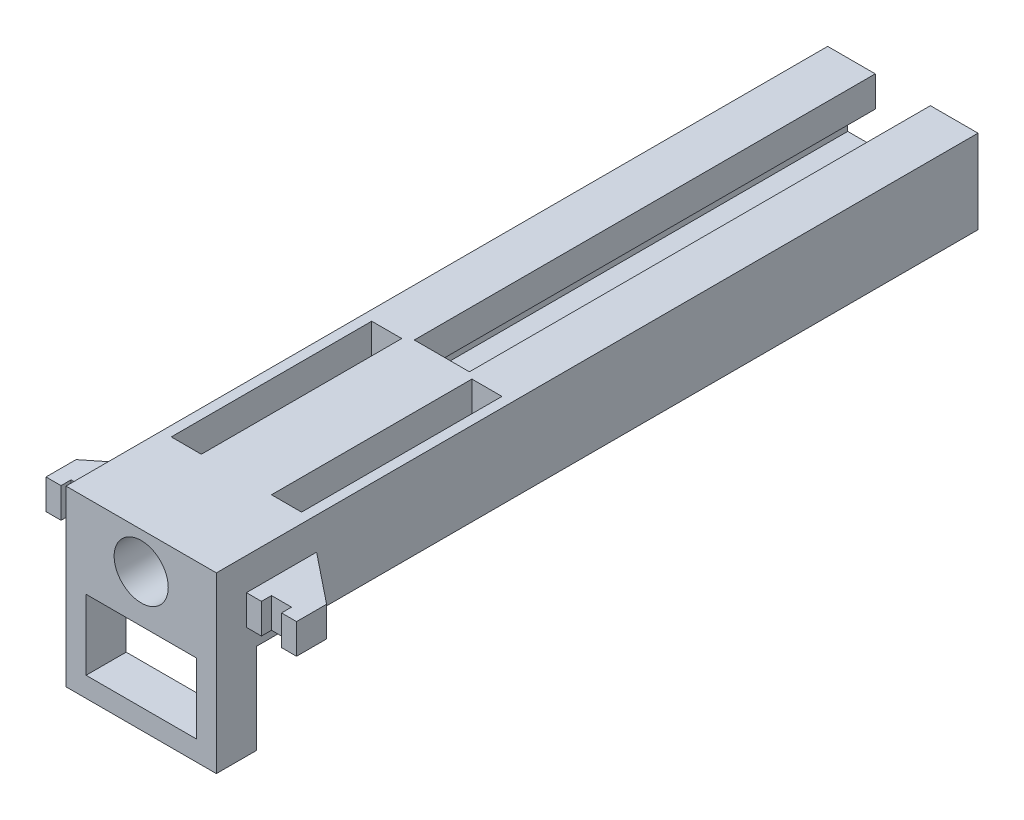
SolidWorks part; units mm, degrees
ref_plane "Front Plane" through (0, 0, 0) normal (0, 0, 1) x (1, 0, 0)
ref_plane "Top Plane" through (0, 0, 0) normal (0, 1, 0) x (1, 0, 0)
ref_plane "Right Plane" through (0, 0, 0) normal (1, 0, 0) x (0, 0, -1)
sketch "Sketch9" plane through (0, 0, 0) normal (0, 0, 1) x (1, 0, 0)
  line L1 (-7.5, 8.35) -> (7.5, 8.35)
  line L2 (-7.5, 8.35) -> (-7.5, 0)
  line L3 (-7.5, 0) -> (7.5, 0)
  line L4 (7.5, 8.35) -> (7.5, 0)
  line L5 (-7.5, 8.35) -> (7.5, 0) construction
  line L6 (-7.5, 0) -> (7.5, 8.35) construction
  point P0 (0, 4.175)
  point P19 (0, 0)
  dimension "D1" = 8.35
  dimension "D2" = 15
extrude "Boss-Extrude4" add sketch "Sketch9" along normal blind 76
sketch "Sketch7" plane through (0, 0, 0) normal (0, 0, 1) x (1, 0, 0)
  line L0 (-5.5, 2) -> (-5.5, 5.3)
  line L1 (-5.5, 5.3) -> (-2.75, 5.3)
  line L2 (-2.75, 5.3) -> (-2.75, 8.35)
  line L3 (-2.75, 8.35) -> (2.75, 8.35) construction
  line L4 (2.75, 8.35) -> (2.75, 5.3)
  line L5 (2.75, 5.3) -> (5.5, 5.3)
  line L6 (5.5, 5.3) -> (5.5, 2)
  line L7 (5.5, 2) -> (-5.5, 2)
  line L9 (7.5, 8.35) -> (-7.5, 8.35) construction
  line L11 (7.5, 0) -> (7.5, 8.35) construction
  line L13 (-2.75, 8.35) -> (2.75, 8.35)
  dimension "D1" = 3.3
  dimension "D2" = 2
  dimension "D3" = 11
  dimension "D4" = 5.5
  dimension "D5" = 2
extrude "Cut-Extrude4" cut sketch "Sketch7" along normal blind 46
sketch "Sketch10" plane through (0, 0, 76) normal (0, 0, 1) x (1, 0, 0)
  line L0 (5.5, 2) -> (-5.5, 2) construction
  circle A0 centre (0, 4.7) radius 2.7
  dimension "D1" = 5.4
extrude "Cut-Extrude5" cut sketch "Sketch10" against normal up to surface (30 mm away) up to face at (0, 5.2375, 46)
sketch "Sketch12" plane through (7.5, 0, 0) normal (1, 0, 0) x (0, 0, -1)
  line L0 (-76, 0) -> (0, 0) construction
  line L1 (-73, 5.14) -> (-70, 5.14)
  line L2 (-73, 5.14) -> (-73, 2.14)
  line L3 (-73, 2.14) -> (-70, 2.14)
  line L4 (-70, 5.14) -> (-70, 2.14)
  line L5 (-73, 5.14) -> (-70, 2.14) construction
  line L6 (-73, 2.14) -> (-70, 5.14) construction
  line L7 (-76, 0) -> (-76, 8.35) construction
  point P0 (-71.5, 3.64)
  dimension "D1" = 3
  dimension "D2" = 3
  dimension "D3" = 2.14
  dimension "D4" = 3
extrude "Boss-Extrude5" add sketch "Sketch12" along normal blind 5
ref_plane "Plane1" through (0, 0, 0) normal (1, 0, 0) x (0, 0, -1)
sketch "Sketch13" plane through (0, 0, 73) normal (0, 0, 1) x (1, 0, 0)
  line L1 (9, 5.14) -> (11, 5.14)
  line L2 (9, 5.14) -> (9, 2.14)
  line L3 (9, 2.14) -> (11, 2.14)
  line L4 (11, 5.14) -> (11, 2.14)
  line L6 (12.5, 5.14) -> (7.5, 5.14) construction
  line L7 (12.5, 2.14) -> (7.5, 2.14) construction
  point P8 (10, 5.14)
  point P9 (10, 5.14)
  dimension "D2" = 2
extrude "Cut-Extrude6" cut sketch "Sketch13" against normal blind 1
mirror "Mirror2" about plane through (0, 0, 0) normal (1, 0, 0) of "Boss-Extrude5"
mirror "Mirror4" about plane through (0, 0, 0) normal (1, 0, 0) of "Cut-Extrude6"
sketch "Sketch14" plane through (0, 5.14, 0) normal (0, 1, 0) x (1, 0, 0)
  line L0 (12.5, -70) -> (7.5, -66)
  line L1 (7.5, -76) -> (7.5, 0) construction
  line L2 (7.5, -66) -> (7.5, -70)
  line L3 (7.5, -70) -> (12.5, -70)
  dimension "D1" = 4
extrude "Boss-Extrude6" add sketch "Sketch14" against normal up to surface (3 mm away) up to face at (10, 2.14, 72)
mirror "Mirror5" about plane through (0, 0, 0) normal (1, 0, 0) of "Boss-Extrude6"
sketch "Sketch15" plane through (0, 8.35, 0) normal (0, 1, 0) x (1, 0, 0)
  line L0 (-7.5, -76) -> (-7.5, 0) construction
  line L1 (-6.5, -66.5) -> (-3.5, -66.5)
  line L2 (-6.5, -66.5) -> (-6.5, -46.5)
  line L3 (-6.5, -46.5) -> (-3.5, -46.5)
  line L4 (-3.5, -66.5) -> (-3.5, -46.5)
  line L5 (-6.5, -66.5) -> (-3.5, -46.5) construction
  line L6 (-6.5, -46.5) -> (-3.5, -66.5) construction
  line L7 (2.75, -46) -> (-2.75, -46) construction
  point P0 (-5, -56.5)
  point P11 (-5, -46.5)
  dimension "D1" = 20
  dimension "D2" = 3
  dimension "D3" = 1
  dimension "D4" = 0.5
extrude "Cut-Extrude7" cut sketch "Sketch15" against normal up to next
mirror "Mirror6" about plane through (0, 0, 0) normal (1, 0, 0) of "Cut-Extrude7"
sketch "Sketch16" plane through (0, 0, 0) normal (0, -1, 0) x (1, 0, 0)
  line L0 (0, -35.8636) -> (0, 35.8636) construction
  line L1 (-7.5, 76) -> (7.5, 76) construction
  circle A0 centre (0, 69) radius 2.5
  dimension "D1" = 5
  dimension "D2" = 7
extrude "Cut-Extrude8" cut sketch "Sketch16" against normal up to surface (2 mm away) up to face at (2.7, 4.7, 76)
sketch "Sketch17" plane through (0, 0, 0) normal (0, -1, 0) x (1, 0, 0)
  line L1 (-7.5, 76) -> (7.5, 76) construction
  line L2 (0, 76) -> (0, 0) construction
  line L3 (-7.5, 76) -> (-7.5, 0) construction
  circle A0 centre (-3, 73.5) radius 1.5
  circle A1 centre (3, 73.5) radius 1.5
  dimension "D1" = 3
  dimension "D2" = 4.5
  dimension "D3" = 2.5
extrude "Boss-Extrude7" [suppressed] add sketch "Sketch17" along normal up to surface (9 mm away)
sketch "Sketch18" plane through (0, 0, 76) normal (0, 0, 1) x (1, 0, 0)
  line L7 (-7.5, 0) -> (7.5, 0) construction
  line L9 (-7.5, 4.175) -> (7.5, 4.175) construction
  line L10 (-7.5, 8.35) -> (-7.5, 0) construction
  line L11 (7.5, 0) -> (7.5, 8.35) construction
  line L12 (-5.5, 0) -> (-7.5, 0)
  line L13 (-5.5, -7) -> (-5.5, 0)
  line L14 (5.5, -7) -> (-5.5, -7)
  line L15 (5.5, 0) -> (5.5, -7)
  line L16 (7.5, 0) -> (5.5, 0)
  line L17 (7.5, -9) -> (7.5, 0)
  line L18 (-7.5, -9) -> (7.5, -9)
  line L19 (-7.5, 0) -> (-7.5, -9)
  dimension "D1" = 2
  dimension "D2" = 2
  dimension "D3" = 9
extrude "Boss-Extrude8" add sketch "Sketch18" against normal blind 4
